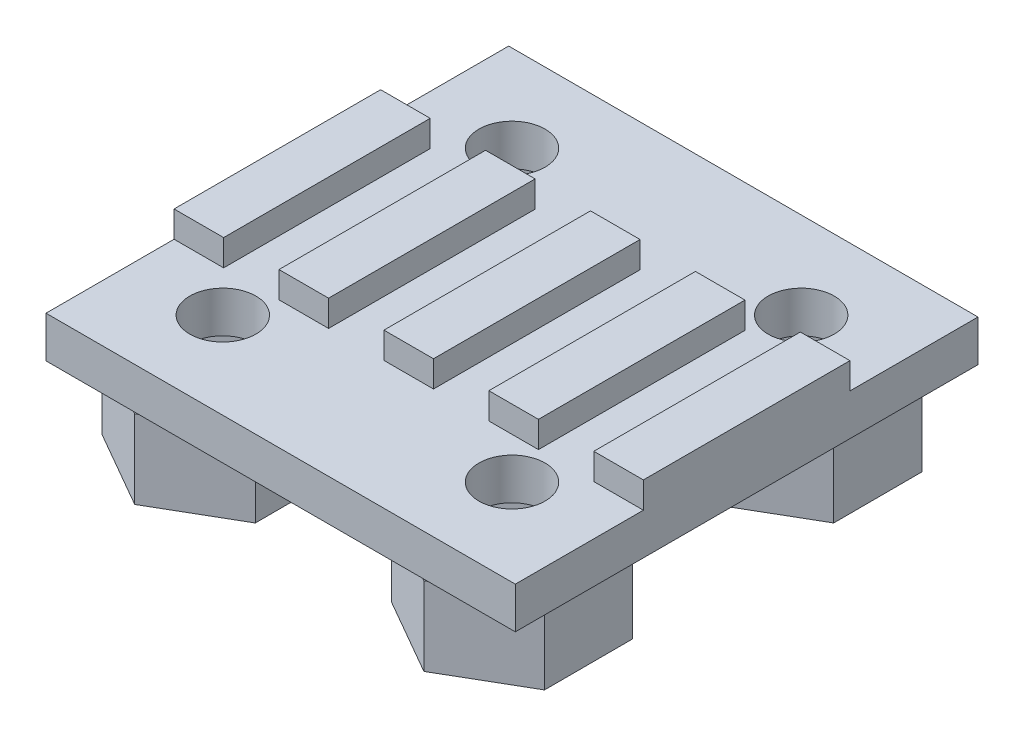
SolidWorks part; units mm, degrees
ref_plane "前视基准面" through (0, 0, 0) normal (0, 0, 1) x (1, 0, 0)
ref_plane "上视基准面" through (0, 0, 0) normal (0, 1, 0) x (1, 0, 0)
ref_plane "右视基准面" through (0, 0, 0) normal (1, 0, 0) x (0, 0, -1)
sketch "草图1" plane through (0, 0, 0) normal (0, 1, 0) x (1, 0, 0)
  line L1 (-11.36, 5) -> (11.36, 5)
  line L2 (-11.36, 5) -> (-11.36, -5)
  line L3 (-11.36, -5) -> (11.36, -5)
  line L4 (11.36, 5) -> (11.36, -5)
  line L5 (-11.36, 5) -> (11.36, -5) construction
  line L6 (-11.36, -5) -> (11.36, 5) construction
  point P0 (0, 0)
  dimension "D1" = 10
  dimension "D2" = 22.72
extrude "主体" add sketch "草图1" along normal blind 2
sketch "草图3" plane through (0, 2, 0) normal (0, 1, 0) x (1, 0, 0)
  line L0 (-11.36, -5) -> (11.36, -5) construction
  line L1 (-1.2, 5) -> (1.2, 5)
  line L2 (-1.2, 5) -> (-1.2, -5)
  line L3 (-1.2, -5) -> (1.2, -5)
  line L4 (1.2, 5) -> (1.2, -5)
  line L5 (-1.2, 5) -> (1.2, -5) construction
  line L6 (-1.2, -5) -> (1.2, 5) construction
  point P0 (0, 0)
  dimension "D1" = 2.4
extrude "凸台-拉伸2" add sketch "草图3" along normal blind 1.27
pattern_linear "阵列(线性)1" count 3 spacing 5.08 along (1, 0, 0) count 3 spacing 5.08 along (-1, 0, 0) of "凸台-拉伸2" pattern seed only yes
sketch "草图4" plane through (0, 0, 0) normal (0, 0, 1) x (1, 0, 0)
  line L0 (8.96, 2) -> (6.28, 2) construction
  line L1 (11.36, 2) -> (-11.36, 2)
  line L2 (11.36, 2) -> (11.36, 0)
  line L3 (11.36, 0) -> (-11.36, 0)
  line L4 (-11.36, 2) -> (-11.36, 0)
  line L5 (11.36, 0) -> (-11.36, 0) construction
  line L6 (-11.36, 3.27) -> (-11.36, 0) construction
  line L7 (11.36, 3.27) -> (11.36, 0) construction
extrude "凸台-拉伸3" add sketch "草图4" along normal blind 6.2 from surface starting at face at (0, 2.435, 5)
extrude "凸台-拉伸4" add sketch "草图4<2>" against normal blind 6.2 from surface starting at face at (0, 2.435, -5)
sketch "草图4<2>" plane through (0, 0, 0) normal (0, 0, 1) x (1, 0, 0) same geometry as "草图4"
sketch "草图6" plane through (0, 0, 0) normal (0, -1, 0) x (-1, 0, 0)
  line L1 (7, -7) -> (-7, -7) construction
  line L2 (7, -7) -> (7, 7) construction
  line L3 (7, 7) -> (-7, 7) construction
  line L4 (-7, -7) -> (-7, 7) construction
  line L5 (7, -7) -> (-7, 7) construction
  line L6 (7, 7) -> (-7, -7) construction
  point P7 (-7, -7)
  point P8 (-7, 7)
  point P9 (7, 7)
  point P13 (7, -7)
  dimension "D1" = 14
  dimension "D2" = 14
sketch "草图5" plane through (0, 0, 0) normal (0, -1, 0) x (1, 0, 0)
  line L1 (7.0062, 10.3486) -> (4.1031, 8.6797)
  line L2 (4.1031, 8.6797) -> (4.0969, 5.3311)
  line L3 (4.0969, 5.3311) -> (6.9938, 3.6514)
  line L4 (6.9938, 3.6514) -> (9.8969, 5.3203)
  line L5 (9.8969, 5.3203) -> (9.9031, 8.6689)
  line L6 (9.9031, 8.6689) -> (7.0062, 10.3486)
  circle A0 centre (7, 7) radius 2.9 construction
  dimension "D1" = 5.8
extrude "拉伸-薄壁1" add sketch "草图5" along normal blind 3.8 thin thin type one direction wall 0.8
pattern_sketch "草图阵列1" of "拉伸-薄壁1" driven by "草图6"
hole_wizard "M3 间隙孔1" positions "草图7" profile "草图8" hole size "M3" standard "ISO" end condition up to next
sketch "草图7" plane through (0, 2, 0) normal (0, 1, 0) x (1, 0, 0)
  point P0 (7, -7)
sketch "草图8" plane through (7, 2, 7) normal (1, 0, 0) x (0, 0, 1)
  line L0 (0, 0) -> (0, 2)
  line L1 (0, 2) -> (1.6, 2)
  line L2 (1.6, 2) -> (1.6, 0)
  line L5 (1.6, 0) -> (0, 0)
  line L11 (0, -6.35) -> (0, 107.95) construction
  dimension "通孔孔直径" = 3.2
  dimension "通孔孔深度" = 2
pattern_sketch "草图阵列2" of "M3 间隙孔1" driven by "草图6"
